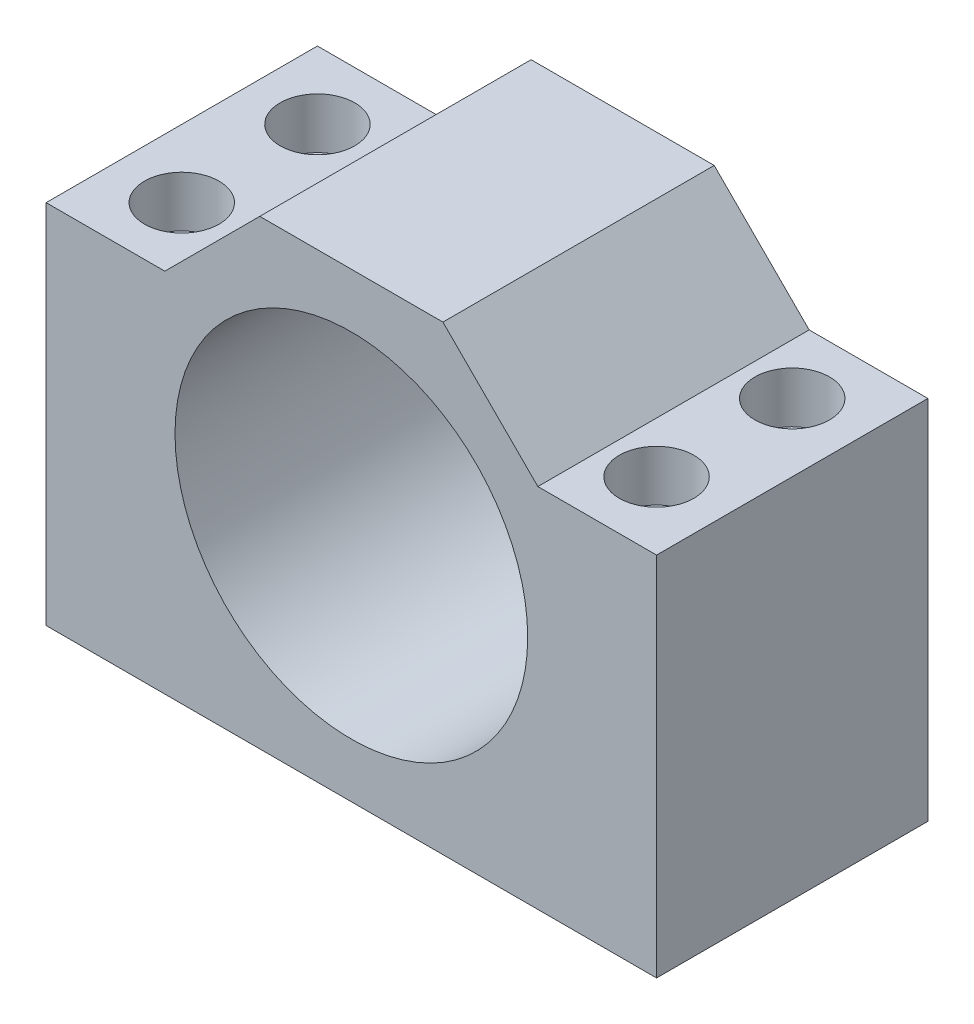
SolidWorks part; units mm, degrees
ref_plane "Front Plane" through (0, 0, 0) normal (0, 0, 1) x (1, 0, 0)
ref_plane "Top Plane" through (0, 0, 0) normal (0, 1, 0) x (1, 0, 0)
ref_plane "Right Plane" through (0, 0, 0) normal (1, 0, 0) x (0, 0, -1)
ref_plane "Plane1"
sketch "Sketch1" plane through (0, 0, 0) normal (0, 0, 1) x (1, 0, 0)
  line L0 (3.8657, -44.0908) -> (93.8657, -44.0908)
  line L1 (93.8657, -44.0908) -> (93.8657, 9.9092)
  line L2 (93.8657, 9.9092) -> (76.3657, 9.9092)
  line L3 (76.3657, 9.9092) -> (62.3657, 23.9092)
  line L4 (62.3657, 23.9092) -> (35.3657, 23.9092)
  line L5 (35.3657, 23.9092) -> (21.3657, 9.9092)
  line L6 (21.3657, 9.9092) -> (3.8657, 9.9092)
  line L7 (3.8657, 9.9092) -> (3.8657, -44.0908)
  circle A0 centre (48.8657, -10.0908) radius 26
  dimension "D7" = 52
  dimension "D1" = 90
  dimension "D2" = 54
  dimension "D3" = 55
  dimension "D4" = 27
  dimension "D5" = 17.5
  dimension "D6" = 19.799
  dimension "D8" = 34
  dimension "D9" = 34
  dimension "D10" = 45
extrude "Extrusion1" add sketch "Sketch1" along normal blind 40 contours L6 L7 L0 L1 L2 L3 L4 L5 A0 region at (4.9937, -17.0908, 0)
hole_wizard "Hole1" positions "Sketch3" profile "Sketch2" counterbore size "M6" standard "ANSI Metric" end condition through all
sketch "Sketch3" plane through (0, 9.9092, 0) normal (0, 1, 0) x (1, 0, 0)
  point P1 (13.8657, -10)
  point P2 (13.8657, -30)
  point P3 (83.8657, -10)
  point P4 (83.8657, -30)
sketch "Sketch2" plane through (13.8657, 9.9092, 10) normal (1, 0, 0) x (0, 0, 1)
  line L0 (0, 0) -> (0, 54)
  line L1 (0, 54) -> (3.3, 54)
  line L3 (3.3, 54) -> (3.3, 7.5)
  line L4 (3.3, 7.5) -> (5.5, 7.5)
  line L5 (5.5, 7.5) -> (5.5, 0)
  line L7 (5.5, 0) -> (0, 0)
  line L11 (0, -6.35) -> (0, 107.95) construction
  dimension "Thru Hole Dia." = 6.6
  dimension "Thru Hole Depth" = 54
  dimension "C'Bore Dia." = 11
  dimension "C'Bore Depth" = 7.5
